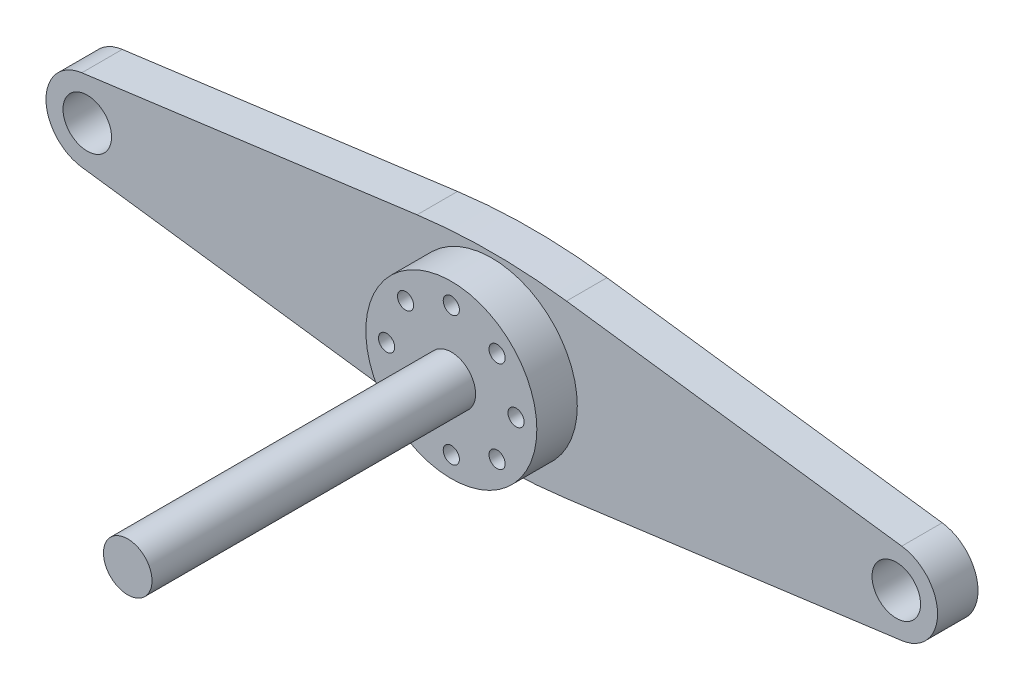
SolidWorks part; units mm, degrees
material "ABS"
ref_plane "Płaszczyzna przednia" through (0, 0, 0) normal (0, 0, 1) x (1, 0, 0)
ref_plane "Płaszczyzna górna" through (0, 0, 0) normal (0, 1, 0) x (1, 0, 0)
ref_plane "Płaszczyzna prawa" through (0, 0, 0) normal (1, 0, 0) x (0, 0, -1)
sketch "Szkic1" plane through (0, 0, 0) normal (0, 0, 1) x (1, 0, 0)
  line L0 (-44.521, 0) -> (57.4684, 0) construction
  line L1 (0, 0) -> (0, 26.3225) construction
  line L2 (-50.6729, 5.0557) -> (-9.2351, 10.5708)
  line L3 (-50.6729, -5.0557) -> (-9.2351, -10.5708)
  line L4 (50.6729, -5.0557) -> (9.2351, -10.5708)
  line L5 (50.6729, 5.0557) -> (9.2351, 10.5708)
  circle A0 centre (0, 0) radius 3
  circle A1 centre (-5.6569, 5.6569) radius 1
  circle A2 centre (-8, 0) radius 1
  circle A3 centre (0, 8) radius 1
  circle A4 centre (5.6569, 5.6569) radius 1
  circle A5 centre (-50, 0) radius 3
  circle A6 centre (50, 0) radius 3
  arc A7 (-50.6729, 5.0557) -> (-50.6729, -5.0557) centre (-50, 0) ccw
  arc A8 (50.6729, 5.0557) -> (50.6729, -5.0557) centre (50, 0) cw
  arc A9 (-9.2351, 10.5708) -> (9.2351, 10.5708) centre (0, -58.8174) cw
  arc A10 (-9.2351, -10.5708) -> (9.2351, -10.5708) centre (0, 58.8174) ccw
  circle A11 centre (8, 0) radius 1
  circle A12 centre (5.6569, -5.6569) radius 1
  circle A13 centre (0, -8) radius 1
  circle A14 centre (-5.6569, -5.6569) radius 1
  circle A15 centre (0, 0) radius 10.5708
  point P16 (0, 0)
  point P28 (0, 11.7999)
  point P31 (0, -11.7999)
  point P41 (0, 0)
  dimension "D1" = 8
  dimension "D2" = 50
  dimension "D3" = 6
  dimension "D4" = 6
  dimension "D5" = 2
  dimension "D6" = 21.1415
  dimension "D7" = 70
  dimension "D8" = 5.1002
  dimension "D9" = 5.6569
  dimension "D10" = 9.2351
extrude "Dodanie-wyciągnięcie1" add sketch "Szkic1" along normal blind 5 contours L3 A10 L4 A8 L5 A9 L2 A7 A15 A6 A5 | A15 A0 A1 A2 A3 A4 A11 A12 A13 A14 | A0 region at (-29.8056, 6.6986, 0) region at (-10.2718, 0, 0)
extrude "Dodanie-wyciągnięcie2" add sketch "Szkic1<3>" along normal blind 10 contours A15 A0 A1 A2 A3 A4 A11 A12 A13 A14 region at (-10.2718, 0, 0)
sketch "Szkic1<3>" plane through (0, 0, 0) normal (0, 0, 1) x (1, 0, 0) same geometry as "Szkic1"
extrude "Dodanie-wyciągnięcie3" add sketch "Szkic1<4>" along normal blind 50 contours A0 region at (0, 0, 0)
sketch "Szkic1<4>" plane through (0, 0, 0) normal (0, 0, 1) x (1, 0, 0) same geometry as "Szkic1"
